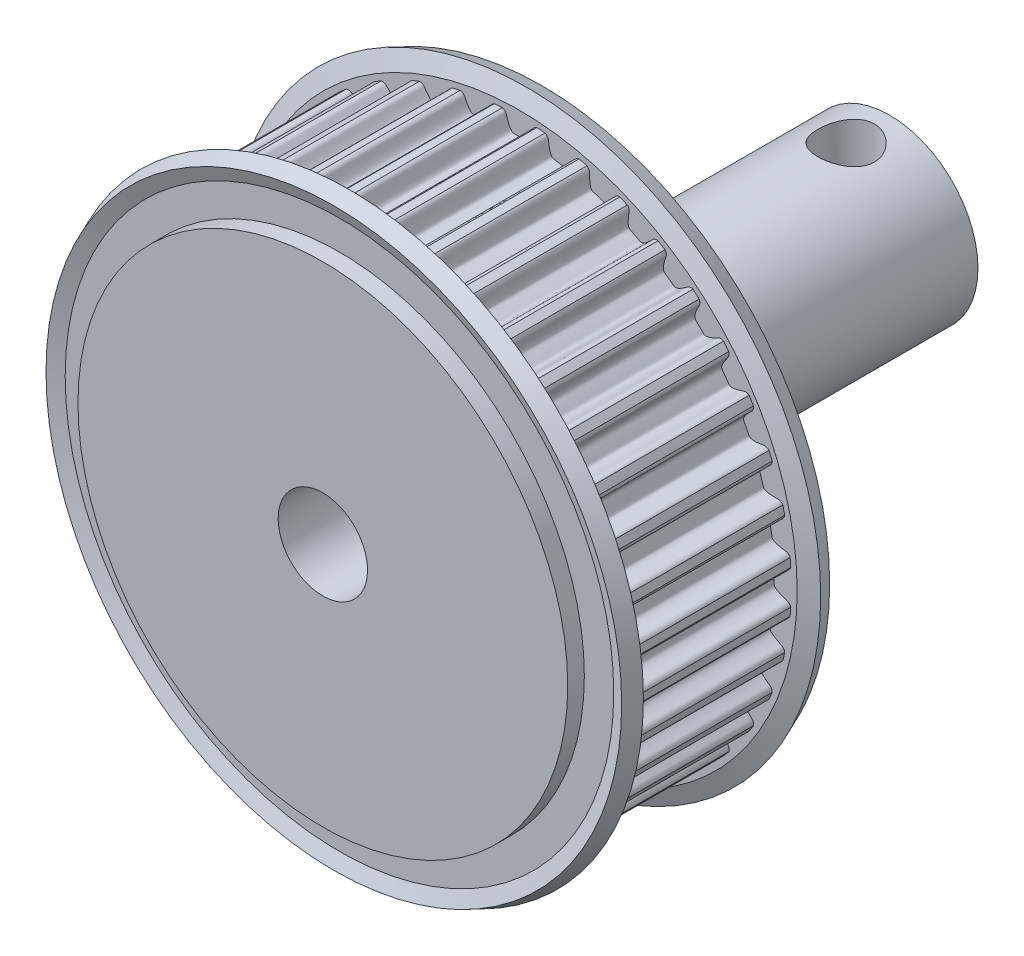
SolidWorks part; units mm, degrees
note: '?' marks a value the reader was unsure of.
ref_plane "前视基准面" through (0, 0, 0) normal (0, 0, 1) x (1, 0, 0)
ref_plane "上视基准面" through (0, 0, 0) normal (0, 1, 0) x (1, 0, 0)
ref_plane "右视基准面" through (0, 0, 0) normal (1, 0, 0) x (0, 0, -1)
other "Configuration Table"
ref_axis "基准轴1" through (0, 0, 55) along (0, 0, -1)?
sketch "SketchRevolveGearBelt01" plane through (0, 0, 0) normal (1, 0, 0) x (0, 0, -1)
  line L0 (0, 0) -> (1, 0) construction
  line L1 (5.274, 0) -> (5.274, 11.2324)
  line L2 (5.274, 11.2324) -> (4.512, 11.2324)
  line L3 (4.512, 11.2324) -> (4.512, 12.5808)
  line L4 (4.512, 12.5808) -> (4.7696, 13.2028)
  line L5 (4.7696, 13.2028) -> (4.0656, 13.4944)
  line L6 (4.0656, 13.4944) -> (3.75, 12.7324)
  line L7 (3.75, 12.7324) -> (3.75, 12.4636)
  line L8 (3.75, 12.4636) -> (-3.75, 12.4636)
  line L9 (-3.75, 12.4636) -> (-3.75, 12.7324)
  line L10 (-3.75, 12.7324) -> (-4.0656, 13.4944)
  line L11 (-4.0656, 13.4944) -> (-4.7696, 13.2028)
  line L12 (-4.7696, 13.2028) -> (-4.512, 12.5808)
  line L13 (-4.512, 12.5808) -> (-4.512, 11.2324)
  line L14 (-4.512, 11.2324) -> (-5.274, 11.2324)
  line L15 (-5.274, 11.2324) -> (-5.274, 0)
  line L16 (-5.274, 0) -> (5.274, 0)
  dimension "GearBeltFlange1OutsideLength" = 1.3484
  dimension "GearBeltFlange1X" = 0.2576
  dimension "GearBeltFlange1Y" = 0.622
  dimension "GearBeltFlangeThickness" = 0.762
  dimension "GearBeltFlangeInside" = 0.2688
  dimension "GearBeltOutsideDiameter" = 12.4636
  dimension "GearBeltFlange2X" = 0.2576
revolve "Gates_PowerGrip_GT_2mm, 6mm Belt Width" add sketch "SketchRevolveGearBelt01" angle 360 about L0
sketch "SketchToothGearBelt01" plane through (0, 0, 0) normal (0, 0, 1) x (1, 0, 0)
  arc A0 (12.4481, 0.8617) -> (12.4481, -0.8617) centre (0, 0) cw
  spline S0 degree 3 poles (12.4481, -0.8617) (12.4481, -0.8443) (12.4457, -0.8183) (12.4374, -0.7846) (12.4288, -0.7601) (12.4179, -0.7365) (12.4047, -0.7141) (12.3893, -0.6931) (12.372, -0.6736) (12.3529, -0.656) (12.3322, -0.6402) (12.31, -0.6266) (12.2867, -0.6151) (12.2476, -0.6013) (12.1977, -0.5862) (12.1386, -0.5675) (12.0861, -0.5498) (12.0368, -0.5322) (11.9907, -0.5145) (11.9478, -0.4969) (11.908, -0.4793) (11.8715, -0.4616) (11.838, -0.444) (11.8078, -0.4264) (11.7807, -0.4087) (11.7568, -0.3911) (11.736, -0.3735) (11.7184, -0.3558) (11.7039, -0.3381) (11.6926, -0.3203) (11.6845, -0.3025) (11.6794, -0.2846) (11.6772, -0.2503) (11.6804, -0.2) (11.6806, -0.1333) (11.6813, -0.0667) (11.6815, 0) (11.6813, 0.0667) (11.6806, 0.1333) (11.6804, 0.2) (11.6772, 0.2503) (11.6794, 0.2846) (11.6845, 0.3025) (11.6926, 0.3203) (11.7039, 0.3381) (11.7184, 0.3558) (11.736, 0.3735) (11.7568, 0.3911) (11.7807, 0.4087) (11.8078, 0.4264) (11.838, 0.444) (11.8715, 0.4616) (11.908, 0.4793) (11.9478, 0.4969) (11.9907, 0.5145) (12.0368, 0.5322) (12.0861, 0.5498) (12.1386, 0.5675) (12.1977, 0.5862) (12.2476, 0.6013) (12.2867, 0.6151) (12.31, 0.6266) (12.3322, 0.6402) (12.3529, 0.656) (12.372, 0.6736) (12.3893, 0.6931) (12.4047, 0.7141) (12.4179, 0.7365) (12.4288, 0.7601) (12.4374, 0.7846) (12.4457, 0.8183) (12.4481, 0.8443) (12.4481, 0.8617) knots 0 0 0 0 0.019856 0.029784 0.039712 0.04964 0.059568 0.069496 0.079424 0.089352 0.09928 0.109208 0.119136 0.129064 0.156684 0.178987 0.200135 0.220136 0.238998 0.256731 0.273348 0.288863 0.303293 0.316663 0.328999 0.340339 0.350727 0.360226 0.368913 0.376892 0.384296 0.39129 0.39807 0.423571 0.449047 0.474524 0.5 0.525476 0.550953 0.576429 0.60193 0.60871 0.615704 0.623108 0.631087 0.639774 0.649273 0.659661 0.671001 0.683337 0.696707 0.711137 0.726652 0.743269 0.761002 0.779864 0.799865 0.821013 0.843316 0.870936 0.880864 0.890792 0.90072 0.910648 0.920576 0.930504 0.940432 0.95036 0.960288 0.970216 0.980144 1 1 1 1
extrude "ToothExtrudeCutGearBelt01" cut sketch "SketchToothGearBelt01" against normal blind 3.75 and the other way blind 3.75
pattern_circular "Tooth Pattern, 40" count 40 every 9 about axis through (0, 0, 55) along (0, 0, -1) of "ToothExtrudeCutGearBelt01"
sketch "BoreRevolveSketch" plane through (0, 0, 0) normal (1, 0, 0) x (0, 0, -1)
  line L0 (0, 0) -> (1, 0) construction
  line L1 (-5.274, 0) -> (5.274, 0)
  line L2 (5.274, 0) -> (5.274, 5)
  line L3 (5.274, 5) -> (-5.274, 5)
  line L4 (-5.274, 5) -> (-5.274, 0)
  dimension "TaperSide1" = 5
  dimension "TaperSide2" = 5
revolve "BoreRevolveCut" cut sketch "BoreRevolveSketch" angle 360 about L0
sketch "AuxiliarySketchGearBelt01" plane through (0, 0, 0) normal (0, 0, 1) x (1, 0, 0)
  circle A0 centre (0, 0) radius 12.7324 construction
  dimension "PitchDiameter" = 25.4648
sketch "草图5" plane through (0, 0, 5.274) normal (0, 0, 1) x (1, 0, 0)
  circle A0 centre (0, 0) radius 5.5465
extrude "凸台-拉伸1" add sketch "草图5" against normal blind 11
sketch "草图6" plane through (0, 0, -5.726) normal (0, 0, -1) x (-1, 0, 0)
  circle A0 centre (0, 0) radius 2.05
  circle A1 centre (0, 0) radius 4.05
  dimension "D1" = 4.1
  dimension "D2" = 2
extrude "凸台-拉伸3" add sketch "草图6" along normal blind 15
sketch "草图7" plane through (0, 0, -5.726) normal (0, 0, -1) x (-1, 0, 0)
  circle A0 centre (0, 0) radius 2.05
extrude "切除-拉伸4" cut sketch "草图7" against normal blind 785
sketch "草图8" plane through (0, 0, -20.726) normal (0, 0, -1) x (-1, 0, 0)
  line L0 (0, 0) -> (0, 1.5)
  line L1 (-1000, 1.5) -> (49000, 1.5)
  circle A0 centre (0, 0) radius 2.0505
  circle M3 centre (0, 0) radius 2.05
  dimension "D1" = 1.5
extrude "凸台-拉伸4" add sketch "草图8" against normal blind 11 contours L1 M3
sketch "草图9" plane through (0, 1.5, 0) normal (0, -1, 0) x (1, 0, 0)
  line L0 (0, -20.726) -> (0, -18.726)
  line L1 (-4.05, -20.726) -> (4.05, -20.726) construction
  line L2 (0, 55) -> (0, -55) construction
  circle A0 centre (0, -18.726) radius 1.3
  dimension "D2" = 2.6
  dimension "D1" = 2
extrude "切除-拉伸5" cut sketch "草图9" against normal blind 11
